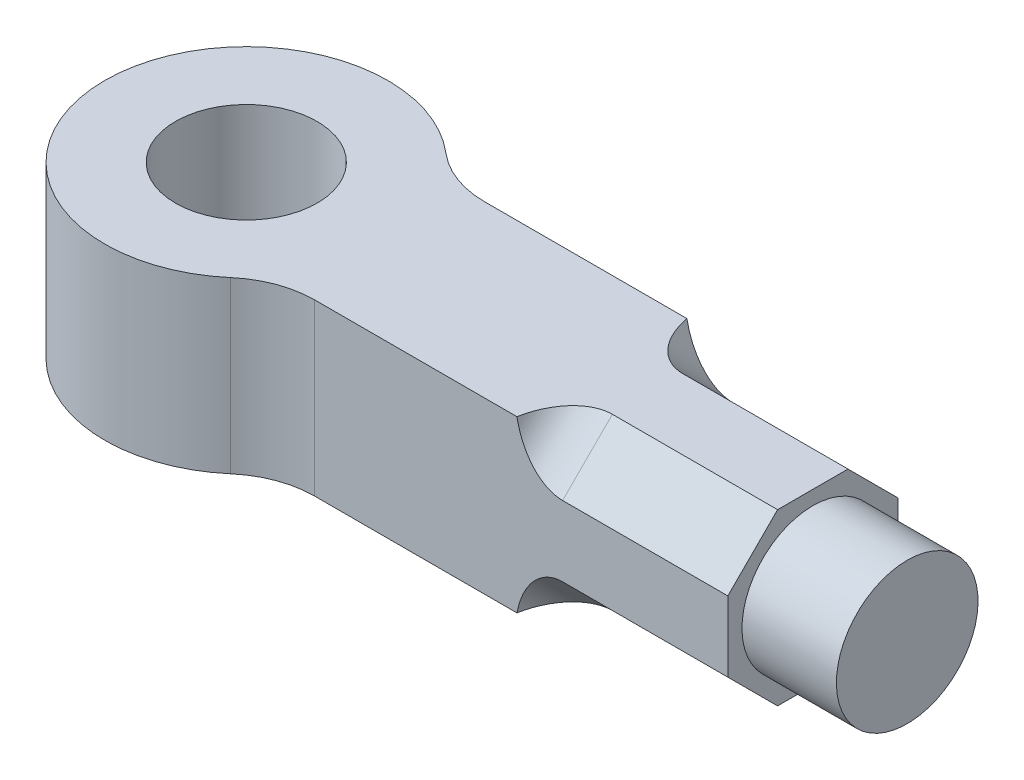
SolidWorks part; units mm, degrees
ref_plane "Front Plane" through (0, 0, 0) normal (0, 0, 1) x (1, 0, 0)
ref_plane "Top Plane" through (0, 0, 0) normal (0, 1, 0) x (1, 0, 0)
ref_plane "Right Plane" through (0, 0, 0) normal (1, 0, 0) x (0, 0, -1)
sketch "Croquis1" plane through (0, 0, 0) normal (0, 1, 0) x (1, 0, 0)
  line L0 (0, 0) -> (120, 0) construction
  line L2 (24, -18) -> (75, -18)
  line L4 (24, 18) -> (75, 18)
  line L5 (75, -18) -> (75, 18)
  line L6 (26.7492, -13.5823) -> (75, 18) construction
  line L7 (26.7492, 13.5823) -> (75, -18) construction
  arc A0 (24, 18) -> (24, -18) centre (0, 0) ccw
  circle A1 centre (0, 0) radius 15
  point P3 (47.5, 0)
  point P10 (42.1353, 0)
  point P11 (47.5, 0)
  point P12 (0, 0)
  dimension "D1" = 60
  dimension "D2" = 30
  dimension "D3" = 120
  dimension "D4" = 45
  dimension "D6" = 36
extrude "Saliente-Extruir2" add sketch "Croquis1" along normal mid plane 36
sketch "Croquis2" plane through (75, 0, 0) normal (1, 0, 0) x (0, 0, -1)
  line L1 (-18, -7.4558) -> (-7.4558, -18)
  line L2 (-7.4558, -18) -> (7.4558, -18)
  line L3 (7.4558, -18) -> (18, -7.4558)
  line L4 (18, -7.4558) -> (18, 7.4558)
  line L5 (18, 7.4558) -> (7.4558, 18)
  line L6 (7.4558, 18) -> (-7.4558, 18)
  line L7 (-7.4558, 18) -> (-18, 7.4558)
  line L8 (-18, 7.4558) -> (-18, -7.4558)
  line L9 (-18, 18) -> (-18, -18) construction
  circle A0 centre (0, 0) radius 18 construction
  dimension "D1" = 36
extrude "Saliente-Extruir3" add sketch "Croquis2" along normal blind 45
fillet "Redondeo1" radius 10 4 edges at (75, -12.7279, 12.7279) (75, -12.7279, -12.7279) (75, 12.7279, -12.7279) (75, 12.7279, 12.7279)
fillet "Redondeo2" radius 20 2 edges at (24, 0, 18) (24, 0, -18)
sketch "Croquis3" plane through (120, 0, 0) normal (1, 0, 0) x (0, 0, -1)
  circle A0 centre (0, 0) radius 15
  dimension "D1" = 30
extrude "Saliente-Extruir4" add sketch "Croquis3" along normal blind 20
